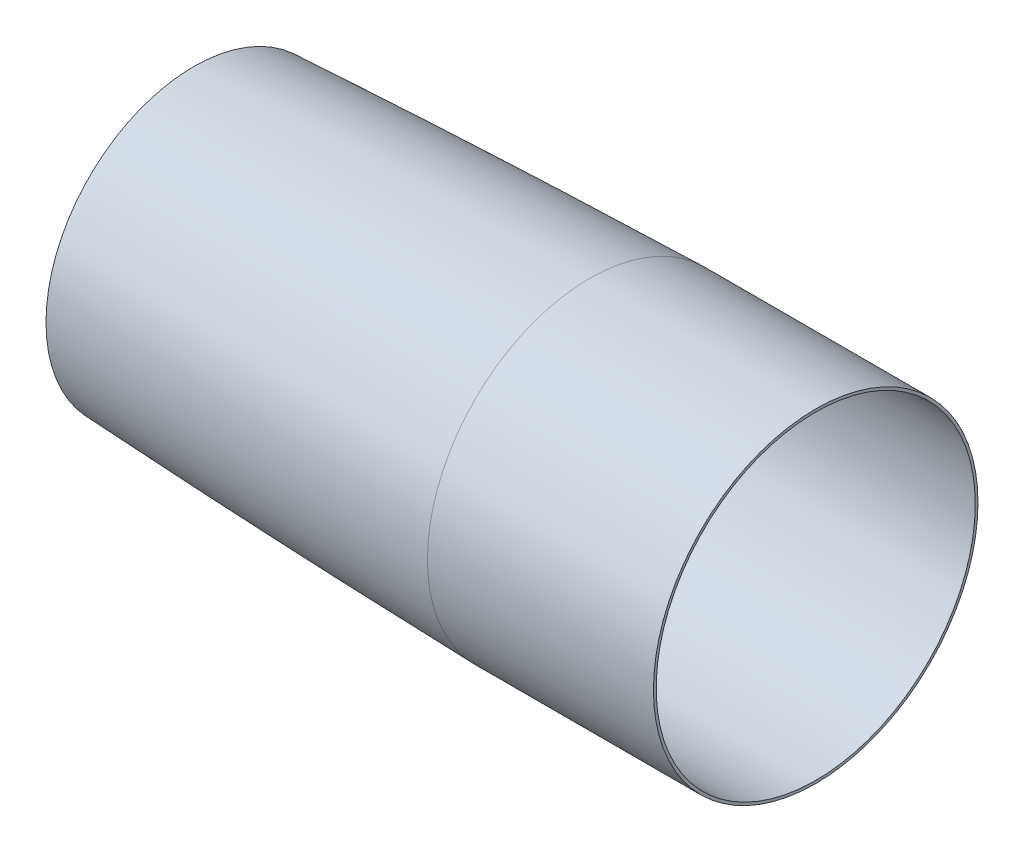
SolidWorks part; units mm, degrees
ref_plane "Front Plane" through (0, 0, 0) normal (0, 0, 1) x (1, 0, 0)
ref_plane "Top Plane" through (0, 0, 0) normal (0, 1, 0) x (1, 0, 0)
ref_plane "Right Plane" through (0, 0, 0) normal (1, 0, 0) x (0, 0, -1)
sketch "Sketch1" plane through (0, 0, 0) normal (0, 1, 0) x (1, 0, 0)
  line L0 (490.97, 48.6046) -> (558.67, 48.6046)
  line L1 (558.67, 48.6046) -> (558.67, 0)
  line L2 (558.67, 0) -> (372.4, 0)
  line L3 (372.4, 0) -> (372.4, 44.2733)
  spline S0 degree 4 poles (360.5413, 43.6674) (361.4311, 43.7137) (363.1505, 43.8029) (365.0659, 43.9041) (370.8829, 44.198) (373.0698, 44.3074) (378.9475, 44.5956) (382.3387, 44.7567) (386.7935, 44.967) (390.6626, 45.1444) (395.6093, 45.3682) (401.3939, 45.6222) (408.3122, 45.917) (416.1851, 46.2379) (424.3361, 46.5563) (432.5048, 46.8598) (440.6158, 47.1478) (448.8413, 47.4237) (456.8671, 47.6805) (465.2386, 47.9307) (472.357, 48.1337) (479.3993, 48.3196) (484.0342, 48.4386) (489.7175, 48.5756) (492.0902, 48.6312) (497.4136, 48.7521) (499.6102, 48.7982) (501.8491, 48.8457) (502.8706, 48.8669) knots 0 0 0 0 0 0.02078 0.041561 0.082618 0.111285 0.139951 0.168618 0.197284 0.225951 0.254617 0.304731 0.362064 0.419398 0.476731 0.534064 0.591397 0.64873 0.706063 0.763396 0.820729 0.859303 0.887969 0.916636 0.944257 0.971877 1 1 1 1 1 construction
  spline S1 degree 4 poles (372.4, 44.2733) (373.2493, 44.3156) (374.9691, 44.4005) (378.9475, 44.5956) (382.3387, 44.7567) (386.7935, 44.967) (390.6626, 45.1444) (395.6093, 45.3682) (401.3939, 45.6222) (408.3122, 45.917) (416.1851, 46.2379) (424.3361, 46.5563) (432.5048, 46.8598) (440.6158, 47.1478) (448.8413, 47.4237) (456.8671, 47.6805) (465.2386, 47.9307) (472.357, 48.1337) (479.3993, 48.3196) (484.0342, 48.4386) (488.4468, 48.545) (490.1199, 48.5847) (490.97, 48.6046) knots 0.082618 0.082618 0.082618 0.082618 0.082618 0.111285 0.139951 0.168618 0.197284 0.225951 0.254617 0.304731 0.362064 0.419398 0.476731 0.534064 0.591397 0.64873 0.706063 0.763396 0.820729 0.859303 0.887969 0.916636 0.916636 0.916636 0.916636 0.916636
revolve "Revolve1" add sketch "Sketch1" angle 360 about L2
shell "Shell1" thickness 1.64 removed face at (372.4, 0, -44.2733)
sketch "Sketch2" plane through (558.67, 0, 0) normal (1, 0, 0) x (0, 0, -1)
  circle A0 centre (0, 0) radius 47.7846
extrude "Cut-Extrude1" cut sketch "Sketch2" against normal blind 67.7
